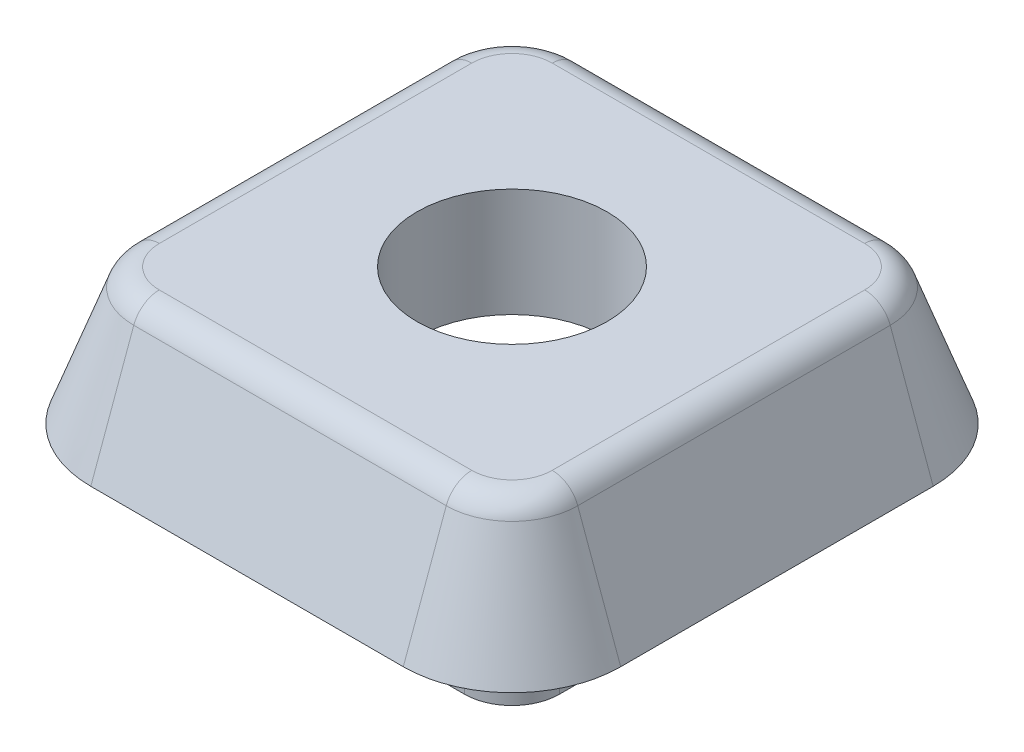
SolidWorks part; units mm, degrees
ref_plane "Front" through (0, 0, 0) normal (0, 0, 1) x (1, 0, 0)
ref_plane "Top" through (0, 0, 0) normal (0, 1, 0) x (1, 0, 0)
ref_plane "Right" through (0, 0, 0) normal (1, 0, 0) x (0, 0, -1)
sketch "Sketch1" plane through (0, 0, 0) normal (0, 1, 0) x (1, 0, 0)
  line L0 (0, 5.6034) -> (0, 0) construction
  line L1 (-5.75, 9.75) -> (5.75, 9.75)
  line L2 (-9.75, 5.75) -> (-9.75, -5.75)
  line L3 (-5.75, -9.75) -> (5.75, -9.75)
  line L4 (9.75, 5.75) -> (9.75, -5.75)
  line L5 (0, 0) -> (12.9658, 0) construction
  line L7 (-5.75, 7.5) -> (5.75, 7.5) construction
  line L8 (-7.5, 5.75) -> (-7.5, -5.75) construction
  line L9 (-5.75, -7.5) -> (5.75, -7.5) construction
  line L10 (7.5, 5.75) -> (7.5, -5.75) construction
  arc A0 (7.5, -5.75) -> (5.75, -7.5) centre (5.75, -5.75) cw construction
  arc A1 (-5.75, -7.5) -> (-7.5, -5.75) centre (-5.75, -5.75) cw construction
  arc A2 (7.5, 5.75) -> (5.75, 7.5) centre (5.75, 5.75) ccw construction
  arc A3 (-7.5, 5.75) -> (-5.75, 7.5) centre (-5.75, 5.75) cw construction
  arc A4 (-9.75, -5.75) -> (-5.75, -9.75) centre (-5.75, -5.75) ccw
  arc A5 (5.75, -9.75) -> (9.75, -5.75) centre (5.75, -5.75) ccw
  arc A6 (5.75, 9.75) -> (9.75, 5.75) centre (5.75, 5.75) cw
  arc A7 (-5.75, 9.75) -> (-9.75, 5.75) centre (-5.75, 5.75) ccw
  dimension "D3" = 1.75
  dimension "D1" = 19.5
  dimension "D2" = 15
extrude "Boss-Extrude1" add sketch "Sketch1" along normal blind 5 draft 20
sketch "Sketch2" plane through (0, 0, 0) normal (0, -1, 0) x (1, 0, 0)
  line L0 (-5.75, 7.5) -> (5.75, 7.5) construction
  line L1 (7.5, -5.75) -> (7.5, 5.75) construction
  line L2 (-5.75, -7.5) -> (5.75, -7.5) construction
  line L3 (-7.5, -5.75) -> (-7.5, 5.75) construction
  line L4 (-5.75, 7.5) -> (5.75, 7.5)
  line L5 (7.5, -5.75) -> (7.5, 5.75)
  line L6 (-5.75, -7.5) -> (5.75, -7.5)
  line L7 (-7.5, -5.75) -> (-7.5, 5.75)
  line L8 (0, 6.1728) -> (0, 0) construction
  line L9 (-5.5, 6.5) -> (5.5, 6.5)
  line L10 (-6.5, 5.5) -> (-6.5, -5.5)
  line L11 (-5.5, -6.5) -> (5.5, -6.5)
  line L12 (6.5, 5.5) -> (6.5, -5.5)
  line L13 (0, 0) -> (5.2896, 0) construction
  line L14 (0, 0) -> (12.9658, 0) construction
  arc A0 (7.5, 5.75) -> (5.75, 7.5) centre (5.75, 5.75) ccw construction
  arc A1 (5.75, -7.5) -> (7.5, -5.75) centre (5.75, -5.75) ccw construction
  arc A2 (-7.5, -5.75) -> (-5.75, -7.5) centre (-5.75, -5.75) ccw construction
  arc A3 (-5.75, 7.5) -> (-7.5, 5.75) centre (-5.75, 5.75) ccw construction
  arc A4 (7.5, 5.75) -> (5.75, 7.5) centre (5.75, 5.75) ccw
  arc A5 (5.75, -7.5) -> (7.5, -5.75) centre (5.75, -5.75) ccw
  arc A6 (-7.5, -5.75) -> (-5.75, -7.5) centre (-5.75, -5.75) ccw
  arc A7 (-5.75, 7.5) -> (-7.5, 5.75) centre (-5.75, 5.75) ccw
  arc A8 (-6.5, -5.5) -> (-5.5, -6.5) centre (-5.5, -5.5) ccw
  arc A9 (5.5, -6.5) -> (6.5, -5.5) centre (5.5, -5.5) ccw
  arc A10 (5.5, 6.5) -> (6.5, 5.5) centre (5.5, 5.5) cw
  arc A11 (-5.5, 6.5) -> (-6.5, 5.5) centre (-5.5, 5.5) ccw
  dimension "D2" = 1
  dimension "D1" = 13
extrude "Boss-Extrude2" add sketch "Sketch2" along normal blind 2
sketch "Sketch3" plane through (0, 0, 0) normal (0, -1, 0) x (1, 0, 0)
  line L0 (5.5, 6.5) -> (-5.5, 6.5) construction
  line L1 (6.5, -5.5) -> (6.5, 5.5) construction
  line L2 (-5.5, -6.5) -> (5.5, -6.5) construction
  line L3 (-6.5, 5.5) -> (-6.5, -5.5) construction
  line L4 (5.5, 6.5) -> (-5.5, 6.5)
  line L5 (6.5, -5.5) -> (6.5, 5.5)
  line L6 (-5.5, -6.5) -> (5.5, -6.5)
  line L7 (-6.5, 5.5) -> (-6.5, -5.5)
  arc A0 (6.5, 5.5) -> (5.5, 6.5) centre (5.5, 5.5) ccw construction
  arc A1 (5.5, -6.5) -> (6.5, -5.5) centre (5.5, -5.5) ccw construction
  arc A2 (-6.5, -5.5) -> (-5.5, -6.5) centre (-5.5, -5.5) ccw construction
  arc A3 (-5.5, 6.5) -> (-6.5, 5.5) centre (-5.5, 5.5) ccw construction
  arc A4 (6.5, 5.5) -> (5.5, 6.5) centre (5.5, 5.5) ccw
  arc A5 (5.5, -6.5) -> (6.5, -5.5) centre (5.5, -5.5) ccw
  arc A6 (-6.5, -5.5) -> (-5.5, -6.5) centre (-5.5, -5.5) ccw
  arc A7 (-5.5, 6.5) -> (-6.5, 5.5) centre (-5.5, 5.5) ccw
extrude "Cut-Extrude1" cut sketch "Sketch3" against normal blind 1
chamfer "Chamfer1" distance 1 angle 45 8 edges at (0, 1, -6.5) (6.2071, 1, -6.2071) (-6.2071, 1, -6.2071) (6.5, 1, 0) (-6.5, 1, 0) (6.2071, 1, 6.2071) (-6.2071, 1, 6.2071) (0, 1, 6.5)
sketch "Sketch4" plane through (0, 1, 0) normal (0, -1, 0) x (1, 0, 0)
  circle A0 centre (0, 0) radius 3.5
  dimension "D1" = 7
extrude "Cut-Extrude2" cut sketch "Sketch4" against normal up to next
fillet "Fillet1" radius 1 8 edges at (-7.2916, 5, 7.2916) (-7.9301, 5, 0) (-7.2916, 5, -7.2916) (0, 5, -7.9301) (7.2916, 5, -7.2916) (7.9301, 5, 0) (7.2916, 5, 7.2916) (0, 5, 7.9301)
